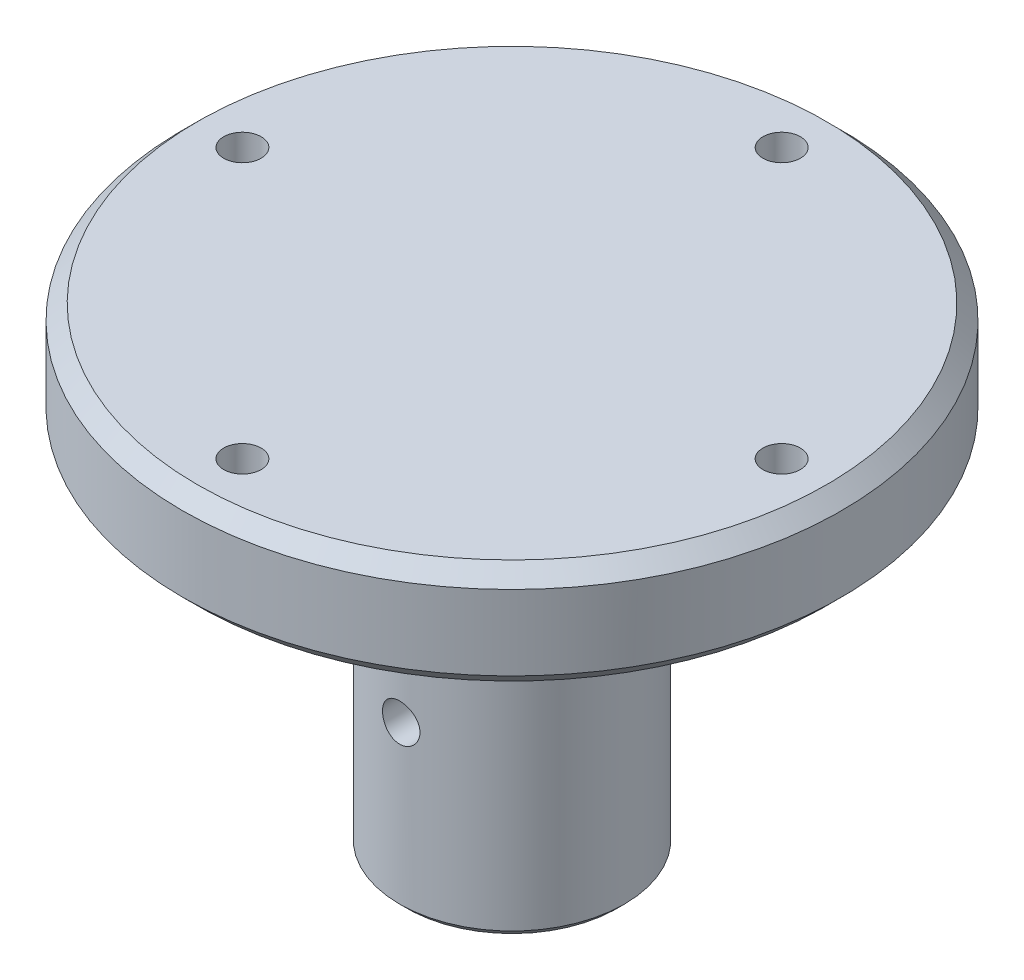
SolidWorks part; units mm, degrees
material "6061 合金"
ref_plane "前视基准面" through (0, 0, 0) normal (0, 0, 1) x (1, 0, 0)
ref_plane "上视基准面" through (0, 0, 0) normal (0, 1, 0) x (1, 0, 0)
ref_plane "右视基准面" through (0, 0, 0) normal (1, 0, 0) x (0, 0, -1)
sketch "草图1" plane through (0, 0, 0) normal (1, 0, 0) x (0, 0, -1)
  line L0 (-7.5, 0) -> (-5.25, 0)
  line L1 (-5.25, 0) -> (-5.25, 18)
  line L2 (-7.5, 0) -> (-7.5, 18)
  line L3 (-7.5, 18) -> (-9, 18)
  line L4 (-9, 18) -> (-9, 21)
  line L5 (-9, 21) -> (-22, 21)
  line L6 (-22, 21) -> (-22, 28)
  line L7 (-22, 28) -> (0, 28)
  line L8 (0, 28) -> (0, -6.0801) construction
  line L9 (-5.25, 18) -> (0, 18)
  line L10 (0, 28) -> (0, 18)
  dimension "D1" = 7
  dimension "D2" = 22
  dimension "D3" = 10
  dimension "D4" = 5.25
  dimension "D5" = 1.5
  dimension "D6" = 18
revolve "旋转1" add sketch "草图1" angle 360 about L8
sketch "草图2" plane through (0, 28, 0) normal (0, 1, 0) x (1, 0, 0)
  line L1 (-5.5, 5.5) -> (5.5, 5.5)
  line L2 (-5.5, 5.5) -> (-5.5, -5.5)
  line L3 (-5.5, -5.5) -> (5.5, -5.5)
  line L4 (5.5, 5.5) -> (5.5, -5.5)
  line L5 (-5.5, 5.5) -> (5.5, -5.5) construction
  line L6 (-5.5, -5.5) -> (5.5, 5.5) construction
  point P0 (0, 0)
  dimension "D1" = 11
  dimension "D2" = 11
sketch "草图5" plane through (0, 0, 0) normal (0, -1, 0) x (1, 0, 0)
  circle A0 centre (0, 0) radius 5.25
  circle A1 centre (0, 0) radius 7.5
extrude "凸台-拉伸1" add sketch "草图5" along normal blind 3.5
sketch "草图6" plane through (0, 0, 0) normal (0, 0, 1) x (1, 0, 0)
  line L1 (-7.5, -3.5) -> (7.5, -3.5) construction
  circle A0 centre (0, 7.5) radius 1.25
  dimension "D1" = 2.5
  dimension "D2" = 11
extrude "M3螺纹孔1" cut sketch "草图6" along normal through all
cosmetic thread "装饰螺纹线1" parameters "D2"=3
chamfer "倒角1" distance 0.5 angle 45 2 edges at (0, -3.5, -7.5) (0, 18, 9)
sketch "草图7" plane through (0, 28, 0) normal (0, 1, 0) x (1, 0, 0)
  circle A0 centre (0, 0) radius 18 construction
  circle A1 centre (0, 18) radius 1.5
  circle A2 centre (18, 0) radius 1.5
  circle A3 centre (0, -18) radius 1.5
  circle A4 centre (-18, 0) radius 1.5
  point P14 (0, 0)
  point P15 (0, 0)
  dimension "D1" = 36
  dimension "D2" = 3
  dimension "D3" = 4
chamfer "倒角2" distance 1 angle 45 2 edges at (0, 21, 22) (0, 28, 22)
sketch "草图8" plane through (0, 21, 0) normal (0, -1, 0) x (1, 0, 0)
  line L0 (-9.8668, 3.5912) -> (-14.0954, 5.1303)
  line L2 (9.8668, 3.5912) -> (14.0954, 5.1303)
  arc A0 (-9.8668, 3.5912) -> (9.8668, 3.5912) centre (0, 0) ccw
  arc A1 (-14.0954, 5.1303) -> (14.0954, 5.1303) centre (0, 0) ccw
  dimension "D1" = 30
  dimension "D2" = 21
extrude "切除-拉伸14" cut sketch "草图8" against normal blind 3.5
fillet "圆角2" radius 2.25 4 edges at (9.8668, 22.75, 3.5912) (14.0954, 22.75, 5.1303) (-9.8668, 22.75, 3.5912) (-14.0954, 22.75, 5.1303)
hole_wizard "M3 螺纹孔1" positions "3D草图1" profile "草图9" tap size "M3" standard "GB" end condition up to next
sketch3d "3D草图1"
  point P0 (0, 28, -18)
  point P3 (18, 28, 0)
  point P6 (0, 28, 18)
  point P9 (-18, 28, 0)
sketch "草图9" plane through (0, 28, -18) normal (1, 0, 0) x (0, 0, 1)
  line L0 (0, 0) -> (0, 7)
  line L1 (0, 7) -> (1.25, 7)
  line L2 (1.25, 7) -> (1.25, 0)
  line L5 (1.25, 0) -> (0, 0)
  line L11 (0, -6.35) -> (0, 107.95) construction
  dimension "通孔螺纹孔钻头直径" = 2.5
  dimension "通孔螺纹孔钻头深度" = 7
cosmetic thread "孔螺蚊线1" parameters "D2"=3
cosmetic thread "孔螺蚊线2" parameters "D2"=3
cosmetic thread "孔螺蚊线3" parameters "D2"=3
cosmetic thread "孔螺蚊线4" parameters "D2"=3
